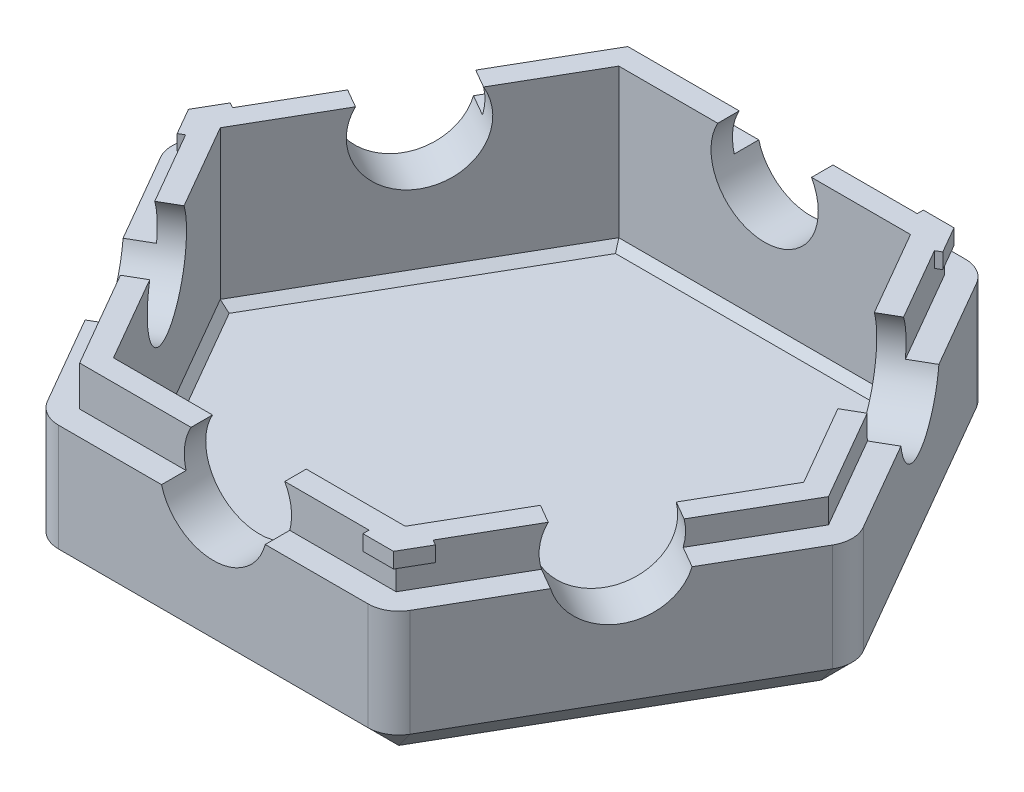
SolidWorks part; units mm, degrees
ref_plane "Front Plane" through (0, 0, 0) normal (0, 0, 1) x (1, 0, 0)
ref_plane "Top Plane" through (0, 0, 0) normal (0, 1, 0) x (1, 0, 0)
ref_plane "Right Plane" through (0, 0, 0) normal (1, 0, 0) x (0, 0, -1)
sketch "Sketch1" plane through (0, 0, 0) normal (0, 1, 0) x (1, 0, 0)
  line L0 (22.5, 0) -> (0, 0) construction
  line L1 (22.5, 0) -> (11.25, 19.4856)
  line L2 (11.25, 19.4856) -> (-11.25, 19.4856)
  line L3 (-11.25, 19.4856) -> (-22.5, 0)
  line L4 (-22.5, 0) -> (-11.25, -19.4856)
  line L5 (-11.25, -19.4856) -> (11.25, -19.4856)
  line L6 (11.25, -19.4856) -> (22.5, 0)
  circle A0 centre (0, 0) radius 19.4856 construction
  dimension "D1" = 22.5
extrude "Boss-Extrude1" add sketch "Sketch1" against normal blind 10 from offset 3.7 offset against normal yes
sketch "Sketch2" plane through (0, -3.7, 0) normal (0, 1, 0) x (1, 0, 0)
  line L0 (19.0359, 0) -> (9.5179, 16.4856)
  line L1 (9.5179, 16.4856) -> (-9.5179, 16.4856)
  line L2 (-9.5179, 16.4856) -> (-19.0359, 0)
  line L3 (-19.0359, 0) -> (-9.5179, -16.4856)
  line L4 (-9.5179, -16.4856) -> (9.5179, -16.4856)
  line L5 (9.5179, -16.4856) -> (19.0359, 0)
  line L6 (11.25, -19.4856) -> (22.5, 0)
  line L7 (22.5, 0) -> (11.25, 19.4856)
  line L8 (11.25, 19.4856) -> (-11.25, 19.4856)
  line L9 (-11.25, 19.4856) -> (-22.5, 0)
  line L10 (-22.5, 0) -> (-11.25, -19.4856)
  line L11 (-11.25, -19.4856) -> (11.25, -19.4856)
  line L12 (11.25, -19.4856) -> (22.5, 0)
  line L13 (22.5, 0) -> (11.25, 19.4856)
  line L14 (11.25, 19.4856) -> (-11.25, 19.4856)
  line L15 (-11.25, 19.4856) -> (-22.5, 0)
  line L16 (-22.5, 0) -> (-11.25, -19.4856)
  line L17 (-11.25, -19.4856) -> (11.25, -19.4856)
  dimension "D1" = 0
  dimension "D2" = 3
extrude "Cut-Extrude1" cut sketch "Sketch2" against normal blind 8.6 contours L4 L5 L0 L1 L2 L3 region at (0, -3.7, 0)
sketch "Sketch3" plane through (0, -3.7, 0) normal (0, 1, 0) x (1, 0, 0)
  line L0 (10.3262, -17.8856) -> (20.6525, 0)
  line L1 (20.6525, 0) -> (10.3262, 17.8856)
  line L2 (10.3262, 17.8856) -> (-10.3262, 17.8856)
  line L3 (-10.3262, 17.8856) -> (-20.6525, 0)
  line L4 (-20.6525, 0) -> (-10.3262, -17.8856)
  line L5 (-10.3262, -17.8856) -> (10.3262, -17.8856)
  line L6 (-9.5179, -16.4856) -> (9.5179, -16.4856)
  line L7 (-19.0359, 0) -> (-9.5179, -16.4856)
  line L8 (-9.5179, 16.4856) -> (-19.0359, 0)
  line L9 (9.5179, 16.4856) -> (-9.5179, 16.4856)
  line L10 (19.0359, 0) -> (9.5179, 16.4856)
  line L11 (9.5179, -16.4856) -> (19.0359, 0)
  line L12 (-9.5179, -16.4856) -> (9.5179, -16.4856)
  line L13 (-19.0359, 0) -> (-9.5179, -16.4856)
  line L14 (-9.5179, 16.4856) -> (-19.0359, 0)
  line L15 (9.5179, 16.4856) -> (-9.5179, 16.4856)
  line L16 (19.0359, 0) -> (9.5179, 16.4856)
  line L17 (9.5179, -16.4856) -> (19.0359, 0)
  dimension "D1" = 0
  dimension "D2" = 1.4
extrude "Boss-Extrude2" add sketch "Sketch3" along normal blind 1.6
fillet "Fillet1" radius 2 6 edges at (22.5, -8.7, 0) (11.25, -8.7, 19.4856) (-11.25, -8.7, 19.4856) (-22.5, -8.7, 0) (-11.25, -8.7, -19.4856) (11.25, -8.7, -19.4856)
sketch "Sketch6" plane through (0, -3.7, 0) normal (0, 1, 0) x (1, 0, 0)
  line L6 (10.3262, -17.8856) -> (20.6525, 0)
  line L7 (-10.3262, -17.8856) -> (10.3262, -17.8856)
  line L8 (-20.6525, 0) -> (-10.3262, -17.8856)
  line L9 (-10.3262, 17.8856) -> (-20.6525, 0)
  line L10 (10.3262, 17.8856) -> (-10.3262, 17.8856)
  line L11 (20.6525, 0) -> (10.3262, 17.8856)
  line L12 (10.3262, -17.8856) -> (20.6525, 0)
  line L13 (-10.3262, -17.8856) -> (10.3262, -17.8856)
  line L14 (-20.6525, 0) -> (-10.3262, -17.8856)
  line L15 (-10.3262, 17.8856) -> (-20.6525, 0)
  line L16 (10.3262, 17.8856) -> (-10.3262, 17.8856)
  line L17 (20.6525, 0) -> (10.3262, 17.8856)
  line L18 (11.8274, -18.4856) -> (21.9226, -1)
  line L19 (21.9226, 1) -> (11.8274, 18.4856)
  line L20 (10.0953, 19.4856) -> (-10.0953, 19.4856)
  line L21 (-11.8274, 18.4856) -> (-21.9226, 1)
  line L22 (-21.9226, -1) -> (-11.8274, -18.4856)
  line L23 (-10.0953, -19.4856) -> (10.0953, -19.4856)
  line L24 (11.8274, -18.4856) -> (21.9226, -1)
  line L25 (21.9226, 1) -> (11.8274, 18.4856)
  line L26 (10.0953, 19.4856) -> (-10.0953, 19.4856)
  line L27 (-11.8274, 18.4856) -> (-21.9226, 1)
  line L28 (-21.9226, -1) -> (-11.8274, -18.4856)
  line L29 (-10.0953, -19.4856) -> (10.0953, -19.4856)
  arc A6 (21.9226, -1) -> (21.9226, 1) centre (20.1906, 0) ccw
  arc A7 (11.8274, 18.4856) -> (10.0953, 19.4856) centre (10.0953, 17.4856) ccw
  arc A8 (-10.0953, 19.4856) -> (-11.8274, 18.4856) centre (-10.0953, 17.4856) ccw
  arc A9 (-21.9226, 1) -> (-21.9226, -1) centre (-20.1906, 0) ccw
  arc A10 (-11.8274, -18.4856) -> (-10.0953, -19.4856) centre (-10.0953, -17.4856) ccw
  arc A11 (10.0953, -19.4856) -> (11.8274, -18.4856) centre (10.0953, -17.4856) ccw
  arc A12 (21.9226, -1) -> (21.9226, 1) centre (20.1906, 0) ccw
  arc A13 (11.8274, 18.4856) -> (10.0953, 19.4856) centre (10.0953, 17.4856) ccw
  arc A14 (-10.0953, 19.4856) -> (-11.8274, 18.4856) centre (-10.0953, 17.4856) ccw
  arc A15 (-21.9226, 1) -> (-21.9226, -1) centre (-20.1906, 0) ccw
  arc A16 (-11.8274, -18.4856) -> (-10.0953, -19.4856) centre (-10.0953, -17.4856) ccw
  arc A17 (10.0953, -19.4856) -> (11.8274, -18.4856) centre (10.0953, -17.4856) ccw
  dimension "D1" = 0
  dimension "D2" = 0
extrude "Cut-Extrude4" cut sketch "Sketch6" against normal blind 1
sketch "Sketch4" plane through (0, 0, -19.4856) normal (0, 0, -1) x (-1, 0, 0)
  line L0 (0, -3.7) -> (0, -3.8) construction
  line L2 (0, -3.7) -> (0, 0) construction
  circle A0 centre (0, -3.8) radius 3.5
  dimension "D2" = 7
  dimension "D1" = 0.1
  dimension "D3" = 3.7
extrude "Cut-Extrude3" cut sketch "Sketch4" against normal up to next
ref_axis "Axis1" through (0, -14.28, 0) along (0, 1, 0)
pattern_circular "CirPattern1" count 6 over 360 about axis through (0, -14.28, 0) along (0, 1, 0) of "Cut-Extrude3"
chamfer "Chamfer1" distance 0.5 angle 45 6 edges at (-14.2769, -12.3, 8.2428) (-14.2769, -12.3, -8.2428) (0, -12.3, -16.4856) (14.2769, -12.3, -8.2428) (14.2769, -12.3, 8.2428) (0, -12.3, 16.4856)
chamfer "Chamfer2" distance 2 angle 45 12 edges at (0, -13.7, 19.4856) (11.0953, -13.7, 19.2176) (-11.0953, -13.7, 19.2176) (16.875, -13.7, 9.7428) (-16.875, -13.7, 9.7428) (22.1906, -13.7, 0) (-22.1906, -13.7, 0) (16.875, -13.7, -9.7428) (-16.875, -13.7, -9.7428) (11.0953, -13.7, -19.2176) (-11.0953, -13.7, -19.2176) (0, -13.7, -19.4856)
sketch "Sketch7" plane through (0, -2.1, 0) normal (0, 1, 0) x (1, 0, 0)
  line L124 (8.5572, 17.8856) -> (8.5572, 18.2856)
  line L125 (10.3262, 17.8856) -> (3.0594, 17.8856) construction
  line L126 (14.1446, 12.0719) -> (10.5572, 18.2856)
  line L127 (10.5572, 18.2856) -> (3.0594, 18.2856)
  line L128 (11.5572, 16.5535) -> (10.5572, 18.2856)
  line L129 (10.5572, 18.2856) -> (8.5572, 18.2856)
  line L130 (11.2108, 16.3535) -> (11.5572, 16.5535)
  line L131 (13.9597, 11.5923) -> (10.3262, 17.8856) construction
  line L132 (13.7982, 11.8719) -> (10.3262, 17.8856) construction
  line L133 (11.2108, 16.3535) -> (10.3262, 17.8856)
  line L134 (10.3262, 17.8856) -> (8.5572, 17.8856)
  line L135 (8.5572, -18.2856) -> (10.5572, -18.2856)
  line L136 (8.5572, -17.8856) -> (10.3262, -17.8856)
  line L137 (10.5572, -18.2856) -> (11.5572, -16.5535)
  line L138 (10.3262, -17.8856) -> (11.2108, -16.3535)
  line L139 (11.2108, -16.3535) -> (11.5572, -16.5535)
  line L140 (8.5572, -17.8856) -> (8.5572, -18.2856)
  line L141 (-20.1144, 1.7321) -> (-21.1144, 0)
  line L142 (-19.7679, 1.5321) -> (-20.6525, 0)
  line L143 (-21.1144, 0) -> (-20.1144, -1.7321)
  line L144 (-20.6525, 0) -> (-19.7679, -1.5321)
  line L145 (-19.7679, -1.5321) -> (-20.1144, -1.7321)
  line L146 (-19.7679, 1.5321) -> (-20.1144, 1.7321)
  point P44 (0, 0)
  dimension "D2" = 2
  dimension "D3" = 2
  dimension "D4" = 3
  dimension "D1" = 0.4
extrude "Boss-Extrude3" add sketch "Sketch7" against normal blind 1
sketch "Sketch9" plane through (0, -2.1, 0) normal (0, 1, 0) x (1, 0, 0)
  line L6 (17.0191, 6.2933) -> (15.8066, 5.5933)
  line L7 (15.8066, 5.5933) -> (19.0359, 0)
  line L8 (19.0359, 0) -> (15.8066, -5.5933)
  line L9 (15.8066, -5.5933) -> (17.0191, -6.2933)
  line L10 (17.0191, -6.2933) -> (20.6525, 0)
  line L11 (20.6525, 0) -> (17.0191, 6.2933)
  line L12 (17.0191, 6.2933) -> (15.8066, 5.5933)
  line L13 (15.8066, 5.5933) -> (19.0359, 0)
  line L14 (19.0359, 0) -> (15.8066, -5.5933)
  line L15 (15.8066, -5.5933) -> (17.0191, -6.2933)
  line L16 (17.0191, -6.2933) -> (20.6525, 0)
  line L17 (20.6525, 0) -> (17.0191, 6.2933)
  dimension "D1" = 0
extrude "Cut-Extrude5" cut sketch "Sketch9" against normal blind 1
